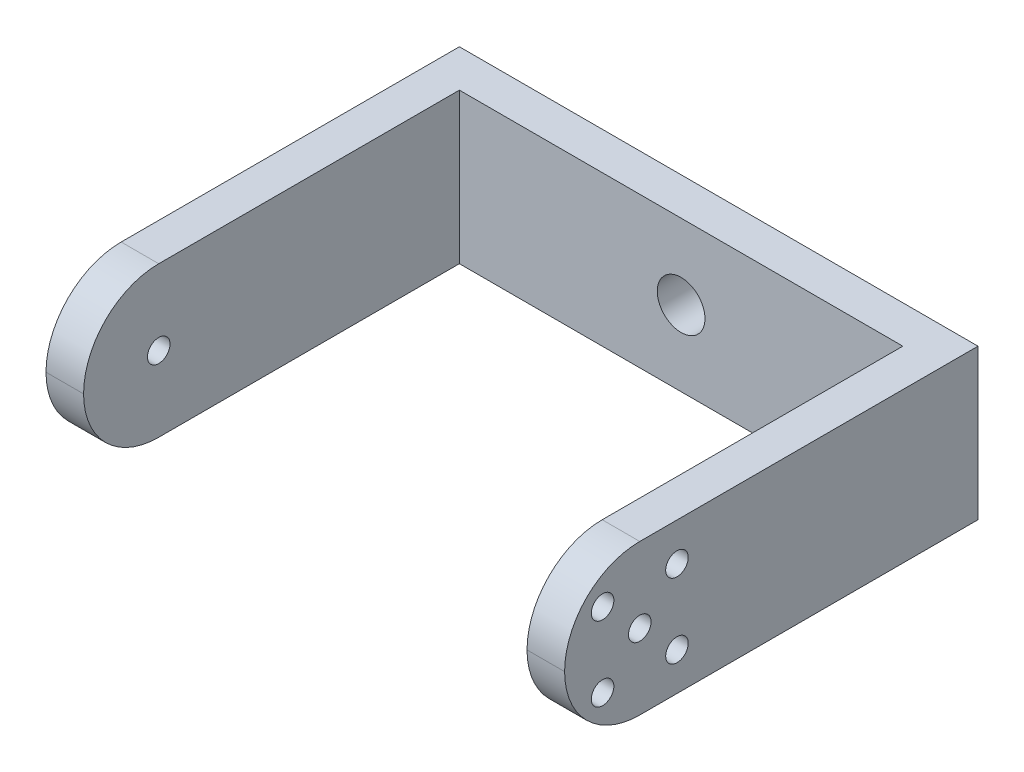
SolidWorks part; units mm, degrees
ref_plane "前视基准面" through (0, 0, 0) normal (0, 0, 1) x (1, 0, 0)
ref_plane "上视基准面" through (0, 0, 0) normal (0, 1, 0) x (1, 0, 0)
ref_plane "右视基准面" through (0, 0, 0) normal (1, 0, 0) x (0, 0, -1)
sketch "草图1" plane through (0, 0, 0) normal (0, 0, 1) x (1, 0, 0)
  line L1 (-34.5, 10) -> (34.5, 10)
  line L2 (-34.5, 10) -> (-34.5, -10)
  line L3 (-34.5, -10) -> (34.5, -10)
  line L4 (34.5, 10) -> (34.5, -10)
  line L5 (-34.5, 10) -> (34.5, -10) construction
  line L6 (-34.5, -10) -> (34.5, 10) construction
  point P0 (0, 0)
extrude "凸台-拉伸1" add sketch "草图1" along normal blind 5
sketch "草图2" plane through (0, 0, 5) normal (0, 0, 1) x (1, 0, 0)
  line L0 (-34.5, 10) -> (-29.5, 10)
  line L1 (34.5, 10) -> (-34.5, 10) construction
  line L2 (-29.5, 10) -> (-29.5, -10)
  line L3 (-34.5, -10) -> (34.5, -10) construction
  line L4 (-29.5, -10) -> (-34.5, -10)
  line L5 (-34.5, -10) -> (-34.5, 10)
  line L6 (34.5, 10) -> (29.5, 10)
  line L7 (29.5, 10) -> (29.5, -10)
  line L8 (29.5, -10) -> (34.5, -10)
  line L9 (34.5, -10) -> (34.5, 10)
extrude "凸台-拉伸2" add sketch "草图2" along normal blind 50
fillet "圆角1" radius 10 4 edges at (-32, -10, 55) (-32, 10, 55) (32, 10, 55) (32, -10, 55)
sketch "草图3" plane through (34.5, 0, 0) normal (1, 0, 0) x (0, 0, -1)
  circle A0 centre (-45, 0) radius 1.5
extrude "切除-拉伸1" cut sketch "草图3" against normal blind 82
sketch "草图4" plane through (34.5, 0, 0) normal (1, 0, 0) x (0, 0, -1)
  circle A0 centre (-49.9497, 4.9497) radius 1.5
  circle A1 centre (-40.0503, 4.9497) radius 1.5
  circle A2 centre (-40.0503, -4.9497) radius 1.5
  circle A3 centre (-49.9497, -4.9497) radius 1.5
  point P0 (-45, 0)
extrude "切除-拉伸2" cut sketch "草图4" against normal blind 10
sketch "草图5" plane through (0, 0, 0) normal (0, 0, -1) x (-1, 0, 0)
  circle A0 centre (0, 0) radius 3.175
extrude "切除-拉伸3" cut sketch "草图5" against normal blind 10
